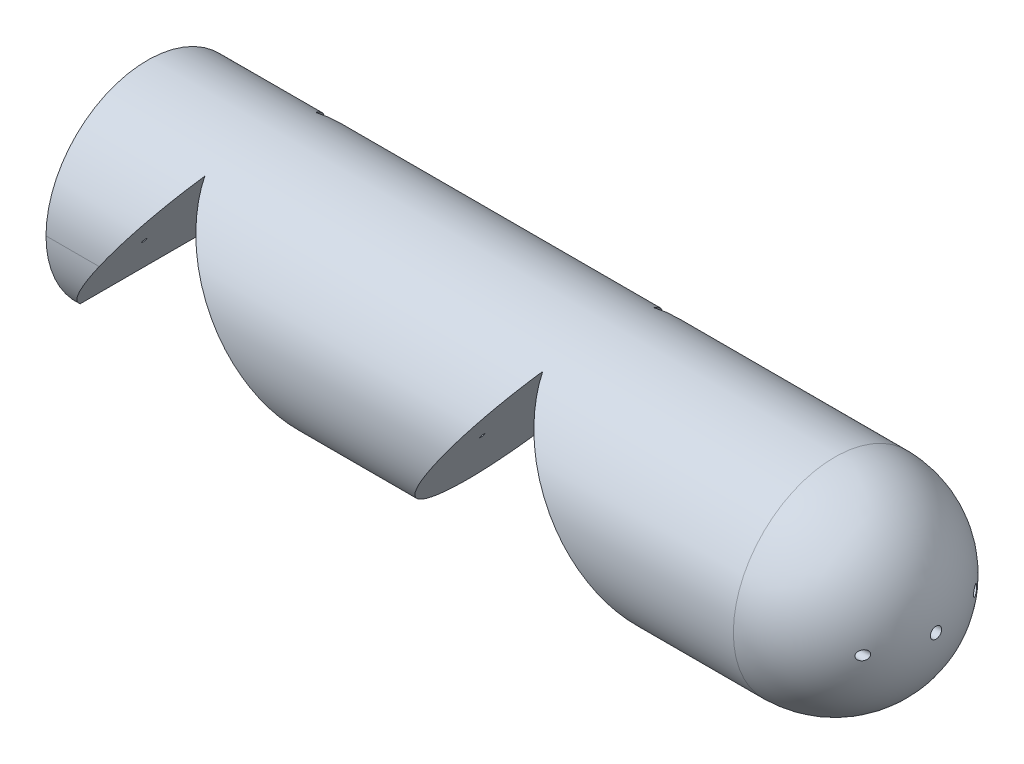
SolidWorks part; units mm, degrees
ref_plane "Front Plane" through (0, 0, 0) normal (0, 0, 1) x (1, 0, 0)
ref_plane "Top Plane" through (0, 0, 0) normal (0, 1, 0) x (1, 0, 0)
ref_plane "Right Plane" through (0, 0, 0) normal (1, 0, 0) x (0, 0, -1)
sketch "Sketch1" plane through (0, 0, 0) normal (0, 0, 1) x (1, 0, 0)
  line L1 (0, 0) -> (70, 0)
  line L2 (0, 0) -> (0, 9)
  line L3 (0, 9) -> (70, 9)
  line L4 (70, 0) -> (70, 9)
  dimension "D1" = 70
  dimension "D2" = 9
revolve "Revolve1" add sketch "Sketch1" angle 360 about L3
fillet "Fillet1" radius 9 1 edges at (70, 9, 9)
sketch "Sketch2" plane through (0, 0, 0) normal (0, 0, 1) x (1, 0, 0)
  line L0 (0, 0) -> (70, 0)
  line L1 (40, 0) -> (40, 16.5429)
  line L2 (40, 16.5429) -> (51.5835, 0)
  line L3 (40, 16.5429) -> (28.4165, 0)
  line L4 (10, 0) -> (10, 16.5429)
  line L5 (10, 16.5429) -> (21.5835, 0)
  line L6 (28.4165, 0) -> (51.5835, 0)
  line L7 (10, 16.5429) -> (-1.5835, 0)
  line L8 (-1.5835, 0) -> (21.5835, 0)
  dimension "D1" = 30
  dimension "D2" = 70
  dimension "D3" = 35
  dimension "D4" = 2
extrude "Cut-Extrude1" cut sketch "Sketch2" against normal mid plane 30 contours L1 L3 L0 | L2 L1 L0 | L0 | L5 L8 L7 region at (36.1388, 5.5143, 0) region at (13.8612, 5.5143, 0) region at (43.8612, 5.5143, 0)
ref_plane "Plane1" through (0, 0, 0) normal (-1, 0, 0) x (0, 0, 1)
sketch "Sketch4" plane through (0, 0, 0) normal (-1, 0, 0) x (0, 0, 1)
  line L0 (-5, 9) -> (5, 9) construction
  circle A0 centre (0, 9) radius 0.2
  circle A1 centre (5, 9) radius 0.2
  circle A2 centre (0, 9) radius 0.2
  circle A3 centre (-5, 9) radius 0.2
  point P5 (0, 9)
  dimension "D1" = 0.4
  dimension "D2" = 10
  dimension "D3" = 2
  dimension "D4" = 2
extrude "Cut-Extrude2" cut sketch "Sketch4" against normal through all contours A3 | L0 A2 | A0 L0 | A1 region at (0, 9.1943, 5) region at (0, 9.0849, 0) region at (0, 8.9151, 0) region at (0, 9, -5.1943)
ref_plane "Plane2" through (69.9978, 0, 0) normal (1, 0, 0) x (0, 0, -1)
sketch "Sketch5" plane through (69.9978, 0, 0) normal (1, 0, 0) x (0, 0, -1)
  circle A0 centre (-5, 9) radius 0.5
  circle A1 centre (0, 9) radius 0.5
  circle A2 centre (5, 9) radius 0.5
  dimension "D1" = 1
  dimension "D2" = 3
extrude "Cut-Extrude3" cut sketch "Sketch5" against normal blind 5 draft 3
